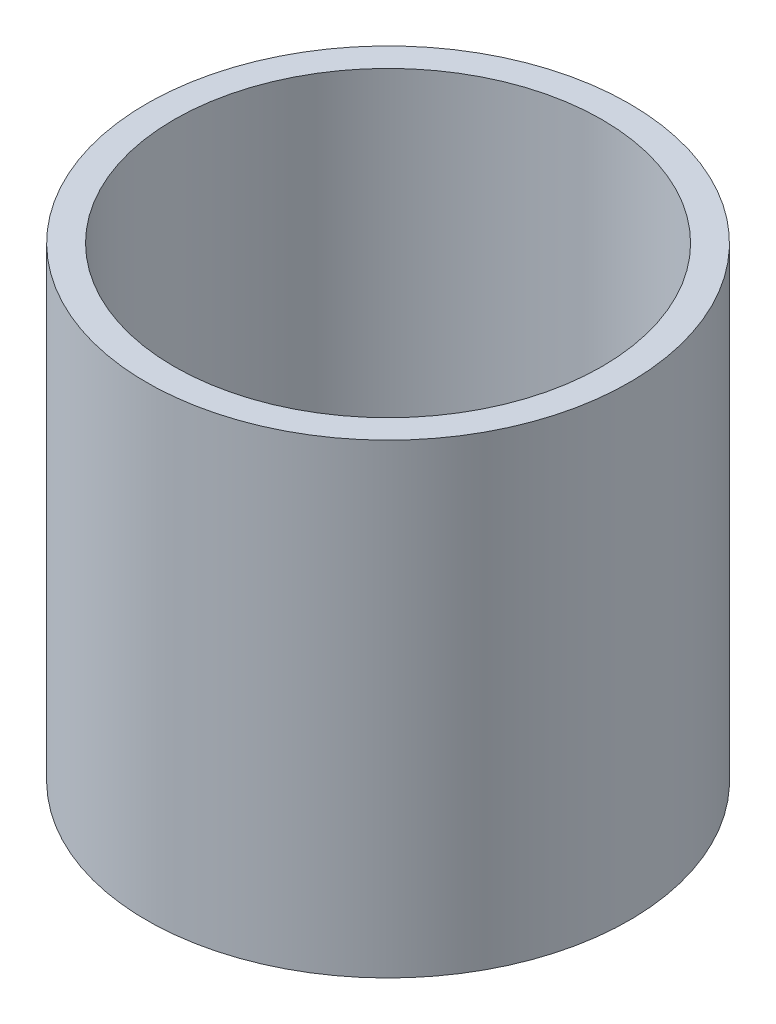
SolidWorks part; units mm, degrees
material "Fireplace Stuff"
ref_plane "Front Plane" through (0, 0, 0) normal (0, 0, 1) x (1, 0, 0)
ref_plane "Top Plane" through (0, 0, 0) normal (0, 1, 0) x (1, 0, 0)
ref_plane "Right Plane" through (0, 0, 0) normal (1, 0, 0) x (0, 0, -1)
sketch "Sketch1" plane through (0, 0, 0) normal (0, 1, 0) x (1, 0, 0)
  circle A0 centre (0, 0) radius 39.5
  circle A1 centre (0, 0) radius 35
  dimension "D1" = 70
  dimension "D2" = 79
extrude "Boss-Extrude1" add sketch "Sketch1" along normal blind 76.2
